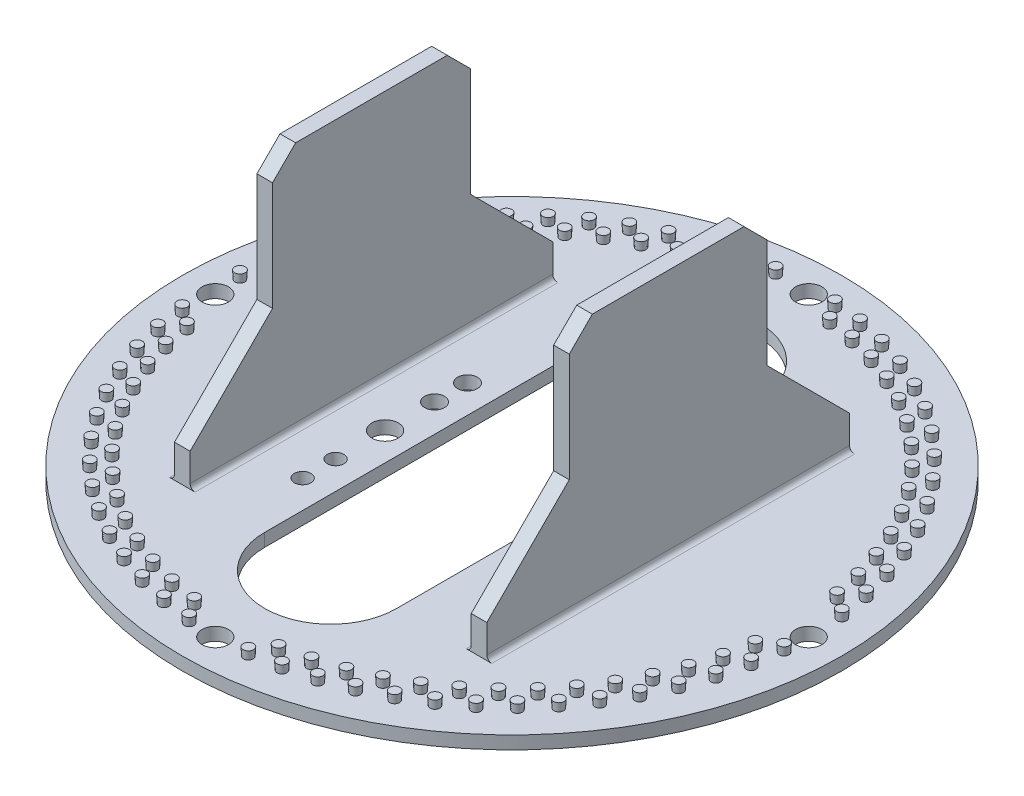
SolidWorks part; units mm, degrees
ref_plane "Front Plane" through (0, 0, 0) normal (0, 0, 1) x (1, 0, 0)
ref_plane "Top Plane" through (0, 0, 0) normal (0, 1, 0) x (1, 0, 0)
ref_plane "Right Plane" through (0, 0, 0) normal (1, 0, 0) x (0, 0, -1)
sketch "Sketch1" plane through (0, 0, 0) normal (0, 1, 0) x (1, 0, 0)
  line L0 (0, -11) -> (0, 11) construction
  line L1 (-4, -11) -> (-4, 11)
  line L2 (4, -11) -> (4, 11)
  circle A0 centre (0, 0) radius 20
  arc A1 (-4, -11) -> (4, -11) centre (0, -11) ccw
  arc A2 (4, 11) -> (-4, 11) centre (0, 11) ccw
  circle A3 centre (0, 18) radius 0.8
  circle A4 centre (0, -18) radius 0.8
  circle A5 centre (18, 0) radius 0.8
  circle A6 centre (-18, 0) radius 0.8
  circle A7 centre (5.7, -2) radius 0.8
  circle A8 centre (-5.7, -2) radius 0.8
  circle A9 centre (-5.7, 1) radius 0.6
  circle A10 centre (-5.7, 3) radius 0.6
  circle A11 centre (-5.7, -5) radius 0.5
  circle A12 centre (-5.7, -7) radius 0.5
  point P5 (0, 0)
  dimension "D1" = 40
  dimension "D3" = 22
  dimension "D2" = 8
  dimension "D6" = 1.6
  dimension "D7" = 1.6
  dimension "D8" = 1.6
  dimension "D10" = 1.6
  dimension "D13" = 1.6
  dimension "D15" = 1.6
  dimension "D18" = 3
  dimension "D4" = 18
  dimension "D5" = 18
  dimension "D9" = 18
  dimension "D11" = 18
  dimension "D12" = 2
  dimension "D14" = 5.7
  dimension "D16" = 2
  dimension "D17" = 5.7
  dimension "D19" = 2
  dimension "D20" = 3
  dimension "D21" = 2
extrude "Boss-Extrude1" add sketch "Sketch1" along normal blind 0.7874
sketch "Sketch6" plane through (0, 0.7874, 0) normal (0, 1, 0) x (1, 0, 0)
  line L0 (0, 0) -> (0, 20) construction
  line L1 (8.5263, 11) -> (9.4737, 11)
  line L2 (8.5263, 11) -> (8.5263, -11)
  line L3 (8.5263, -11) -> (9.4737, -11)
  line L4 (9.4737, 11) -> (9.4737, -11)
  line L5 (8.5263, 11) -> (9.4737, -11) construction
  line L6 (8.5263, -11) -> (9.4737, 11) construction
  line L7 (-8.5263, -11) -> (-9.4737, -11)
  line L8 (-8.5263, 11) -> (-8.5263, -11)
  line L9 (-8.5263, 11) -> (-9.4737, 11)
  line L10 (-9.4737, 11) -> (-9.4737, -11)
  circle A0 centre (0, 0) radius 20 construction
  point P0 (9, 0)
  dimension "D1" = 9
  dimension "D2" = 22
extrude "Boss-Extrude2" add sketch "Sketch6" along normal blind 15
sketch "Sketch7" plane through (0, 0, 0) normal (1, 0, 0) x (0, 0, -1)
  line L0 (-11, 2.7874) -> (-6, 7.7874)
  line L1 (-11, 15.7874) -> (-11, 0.7874) construction
  line L2 (-6, 7.7874) -> (-6, 14.3874)
  line L3 (-6, 14.3874) -> (-4.6, 15.7874)
  line L4 (-11, 15.7874) -> (11, 15.7874) construction
  line L5 (0, 15.7874) -> (0, 0.7874) construction
  line L7 (-11, 0.7874) -> (11, 0.7874) construction
  line L8 (-11, 2.7874) -> (-11, 15.7874)
  line L9 (-11, 15.7874) -> (-4.6, 15.7874)
  line L10 (11, 2.7874) -> (11, 15.7874)
  line L11 (11, 2.7874) -> (6, 7.7874)
  line L12 (6, 7.7874) -> (6, 14.3874)
  line L13 (6, 14.3874) -> (4.6, 15.7874)
  line L14 (11, 15.7874) -> (4.6, 15.7874)
  dimension "D1" = 2
  dimension "D2" = 7
  dimension "D3" = 45
  dimension "D4" = 1.4
  dimension "D5" = 135
extrude "Cut-Extrude1" cut sketch "Sketch7" against normal mid plane 30
sketch "Sketch8" plane through (0, 0.7874, 0) normal (0, 1, 0) x (1, 0, 0)
  circle A0 centre (18, 2.0081) radius 0.3173
extrude "Boss-Extrude3" add sketch "Sketch8" against normal blind 2 draft 3 from offset 0.5
ref_axis "Axis1" through (0, -1.5376, 0) along (0, 1, 0)
pattern_circular "CirPattern4" count 64 over 360 about axis through (0, -1.5376, 0) along (0, 1, 0) skipping 15, 31, 47, 63 of "Boss-Extrude3"
sketch "Sketch9" plane through (0, 0.7874, 0) normal (0, 1, 0) x (1, 0, 0)
  circle A0 centre (16.9409, 2.7781) radius 0.3173
extrude "Boss-Extrude4" add sketch "Sketch9" against normal blind 2 draft 3 from offset 0.5
pattern_circular "CirPattern5" count 64 over 360 about axis through (0, -1.5376, 0) along (0, 1, 0) skipping 14, 15, 30, 31, 46, 47, 62, 63 of "Boss-Extrude4"
fillet "Fillet1" radius 0.3 4 edges at (-8.5263, 0.7874, 0) (-9.4737, 0.7874, 0) (8.5263, 0.7874, 0) (9.4737, 0.7874, 0)
